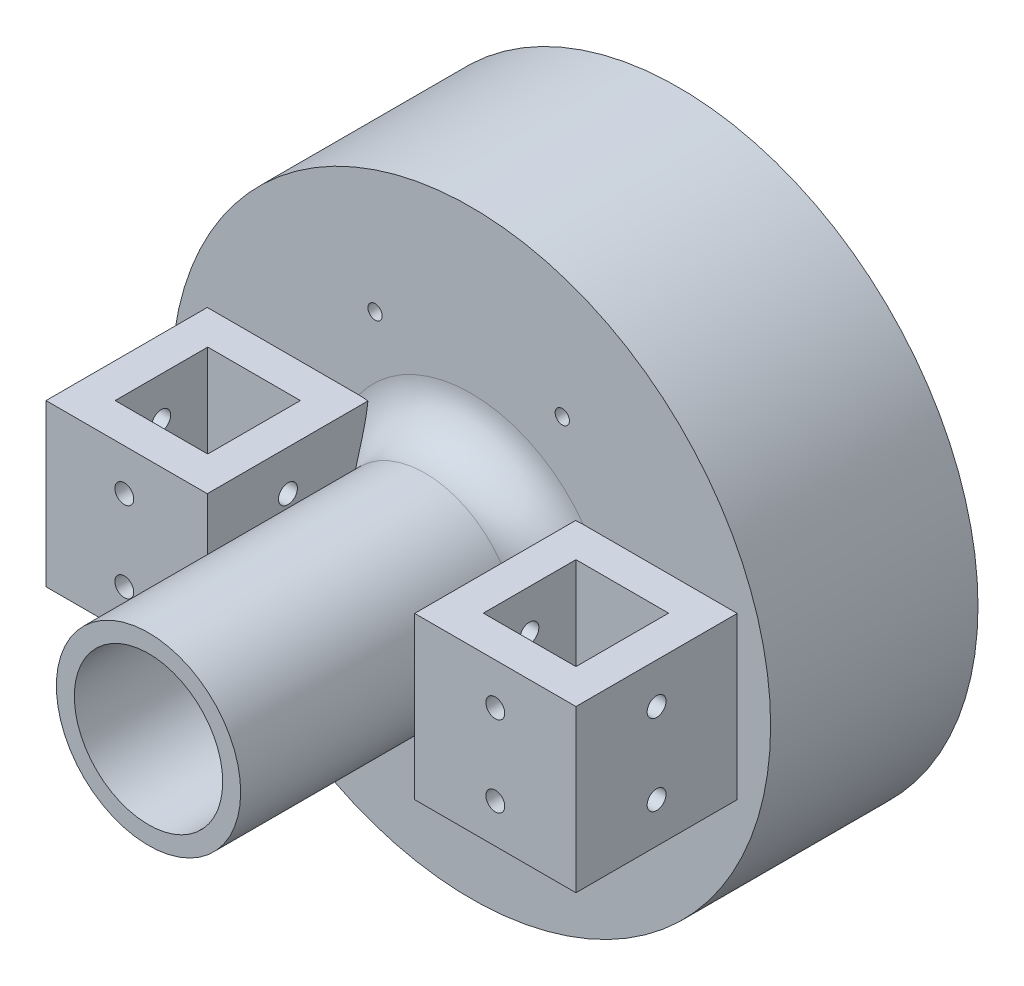
SolidWorks part; units mm, degrees
ref_plane "Front Plane" through (0, 0, 0) normal (0, 0, 1) x (1, 0, 0)
ref_plane "Top Plane" through (0, 0, 0) normal (0, 1, 0) x (1, 0, 0)
ref_plane "Right Plane" through (0, 0, 0) normal (1, 0, 0) x (0, 0, -1)
sketch "Sketch1" plane through (0, 0, 0) normal (0, 0, 1) x (1, 0, 0)
  line L0 (-64.3545, 9.1377) -> (64.3545, -9.1377) construction
  circle A0 centre (0, 0) radius 65
  circle A6 centre (-19.7854, -35.4819) radius 1.55
  circle A7 centre (0, 0) radius 16.5
  circle A11 centre (-40.621, -0.6063) radius 1.55
  circle A12 centre (-20.8355, 34.8757) radius 1.55
  circle A13 centre (19.7854, 35.4819) radius 1.55
  circle A14 centre (40.621, 0.6063) radius 1.55
  circle A15 centre (20.8355, -34.8757) radius 1.55
  point P18 (0, 0)
  point P20 (0, 0)
  point P36 (0, 0)
  dimension "D1" = 130
  dimension "D2" = 6
  dimension "D5" = 33
  dimension "D3" = 40.6255
extrude "Boss-Extrude1" add sketch "Sketch1" along normal blind 10
sketch "Sketch2" plane through (0, 0, 10) normal (0, 0, 1) x (1, 0, 0)
  circle A0 centre (0, 0) radius 20
  circle A1 centre (0, 0) radius 16.1
  dimension "D1" = 40
  dimension "D2" = 32.2
extrude "Boss-Extrude2" add sketch "Sketch2" along normal blind 70
sketch "Sketch3" plane through (0, 0, 0) normal (0, 0, -1) x (-1, 0, 0)
  circle A0 centre (0, 0) radius 45.25
  circle A1 centre (0, 0) radius 65
  dimension "D1" = 90.5
extrude "Boss-Extrude3" add sketch "Sketch3" along normal blind 35
sketch "Sketch4" plane through (0, 0, 10) normal (0, 0, 1) x (1, 0, 0)
  line L0 (-65, 0) -> (65, 0) construction
  line L1 (-57.2457, 17.5) -> (-22.2457, 17.5)
  line L2 (-57.2457, 17.5) -> (-57.2457, -17.5)
  line L3 (-57.2457, -17.5) -> (-22.2457, -17.5)
  line L4 (-22.2457, 17.5) -> (-22.2457, -17.5)
  line L5 (-57.2457, 17.5) -> (-22.2457, -17.5) construction
  line L6 (-57.2457, -17.5) -> (-22.2457, 17.5) construction
  line L7 (22.7543, 17.5) -> (57.7543, 17.5)
  line L8 (22.7543, 17.5) -> (22.7543, -17.5)
  line L9 (22.7543, -17.5) -> (57.7543, -17.5)
  line L10 (57.7543, 17.5) -> (57.7543, -17.5)
  line L11 (22.7543, 17.5) -> (57.7543, -17.5) construction
  line L12 (22.7543, -17.5) -> (57.7543, 17.5) construction
  circle A0 centre (40.3888, -6.3107) radius 1.55 construction
  circle A1 centre (-39.7457, -0.7631) radius 1.55 construction
  circle A2 centre (0, 0) radius 65 construction
  point P21 (40.2543, 0)
  point P22 (-39.7457, 0)
  point P23 (-22.2457, 0)
  dimension "D1" = 35
  dimension "D2" = 35
  dimension "D3" = 35
  dimension "D4" = 35
  dimension "D5" = 45
  dimension "D6" = 22.2457
extrude "Boss-Extrude4" add sketch "Sketch4" along normal blind 35
sketch "Sketch5" plane through (0, 17.5, 0) normal (0, 1, 0) x (1, 0, 0)
  line L0 (57.7543, -45) -> (57.7543, -10) construction
  line L1 (30.1543, -17.4) -> (50.2543, -17.4)
  line L2 (30.1543, -17.4) -> (30.1543, -37.5)
  line L3 (30.1543, -37.5) -> (50.2543, -37.5)
  line L4 (50.2543, -17.4) -> (50.2543, -37.5)
  line L5 (30.1543, -17.4) -> (50.2543, -37.5) construction
  line L6 (30.1543, -37.5) -> (50.2543, -17.4) construction
  line L7 (-49.7457, -17.4) -> (-29.6457, -17.4)
  line L8 (-49.7457, -17.4) -> (-49.7457, -37.5)
  line L9 (-49.7457, -37.5) -> (-29.6457, -37.5)
  line L10 (-29.6457, -17.4) -> (-29.6457, -37.5)
  line L11 (-49.7457, -17.4) -> (-29.6457, -37.5) construction
  line L12 (-49.7457, -37.5) -> (-29.6457, -17.4) construction
  line L13 (57.7543, -45) -> (22.7543, -45) construction
  line L14 (-57.2457, -45) -> (-57.2457, -10) construction
  line L15 (-22.2457, -45) -> (-57.2457, -45) construction
  point P0 (40.2043, -27.45)
  point P5 (-39.6957, -27.45)
  dimension "D1" = 20.1
  dimension "D2" = 20.1
  dimension "D3" = 7.5
  dimension "D4" = 7.5
  dimension "D5" = 20.1
  dimension "D6" = 20.1
  dimension "D7" = 7.5
  dimension "D8" = 7.5
extrude "Cut-Extrude1" cut sketch "Sketch5" against normal blind 40
fillet "Fillet1" radius 10 1 edges at (20, 0, 10)
sketch "Sketch6" plane through (57.7543, 0, 0) normal (1, 0, 0) x (0, 0, -1)
  line L0 (-27.5, 17.5) -> (-27.5, -17.5) construction
  line L1 (-45, 17.5) -> (-10, 17.5) construction
  line L2 (-45, -17.5) -> (-10, -17.5) construction
  line L3 (-45, 0) -> (-10, 0) construction
  line L4 (-45, -17.5) -> (-45, 17.5) construction
  line L5 (-10, 65) -> (-10, -65) construction
  circle A0 centre (-27.5, 8.75) radius 2.05
  circle A1 centre (-27.5, -8.75) radius 2.05
  point P16 (-27.5, 0)
  dimension "D1" = 4.1
  dimension "D2" = 4.1
  dimension "D3" = 8.75
  dimension "D4" = 8.75
extrude "Cut-Extrude2" cut sketch "Sketch6" against normal blind 127
sketch "Sketch7" plane through (0, 0, 45) normal (0, 0, 1) x (1, 0, 0)
  line L0 (24.367, -17.5) -> (57.7543, -17.5) construction
  line L1 (22.7543, 17.5) -> (22.7543, -17.5) construction
  line L2 (0, 0) -> (0, -6.0051) construction
  circle A0 centre (40.2543, 8.5) radius 2.05
  circle A1 centre (40.2543, -9) radius 2.05
  circle A2 centre (-40.2543, -9) radius 2.05
  circle A3 centre (-40.2543, 8.5) radius 2.05
  dimension "D1" = 4.1
  dimension "D2" = 4.1
  dimension "D3" = 17.5
  dimension "D4" = 8.5
  dimension "D5" = 17.5
extrude "Cut-Extrude3" cut sketch "Sketch7" along normal blind 1 and the other way blind 16
